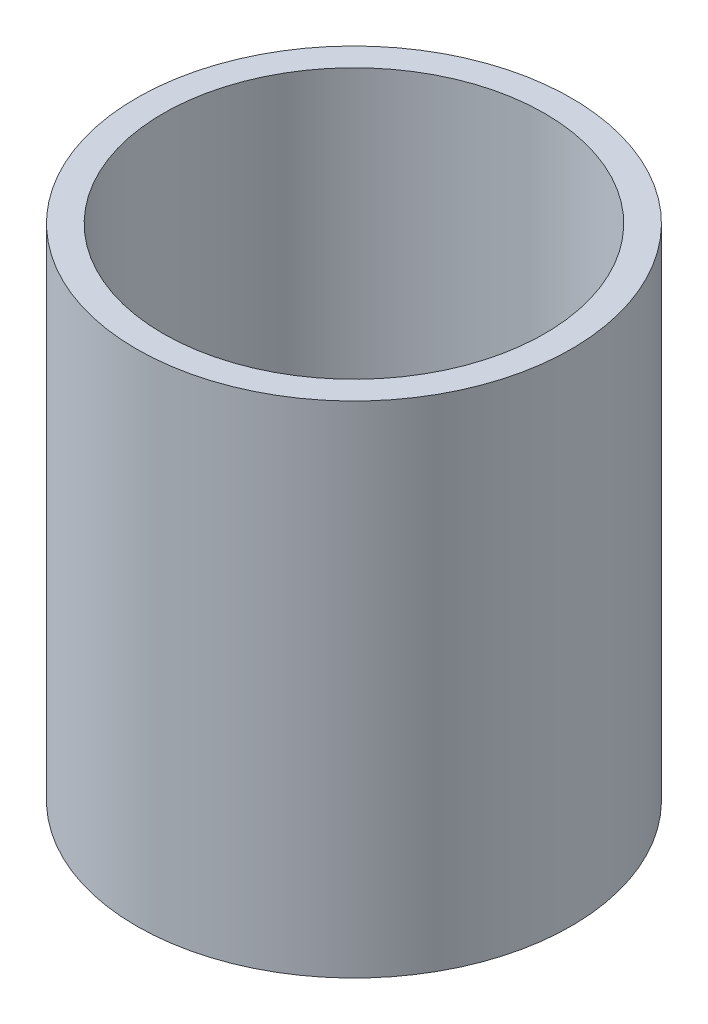
SolidWorks part; units mm, degrees
ref_plane "Front Plane" through (0, 0, 0) normal (0, 0, 1) x (1, 0, 0)
ref_plane "Top Plane" through (0, 0, 0) normal (0, 1, 0) x (1, 0, 0)
ref_plane "Right Plane" through (0, 0, 0) normal (1, 0, 0) x (0, 0, -1)
sketch "Sketch1" plane through (0, 0, 0) normal (0, 1, 0) x (1, 0, 0)
  circle A0 centre (0, 0) radius 27.5
  dimension "SLEEVE_OD" = 55
extrude "Boss-Extrude1" add sketch "Sketch1" along normal blind 63.2036
sketch "Sketch2" plane through (0, 0, 0) normal (0, 1, 0) x (1, 0, 0)
  circle A0 centre (0, 0) radius 24.1297
  dimension "BORE_D" = 48.2595
extrude "Cut-Extrude1" cut sketch "Sketch2" along normal through all
chamfer "Chamfer1" distance 2.3993 angle 45 rebuild error yes
